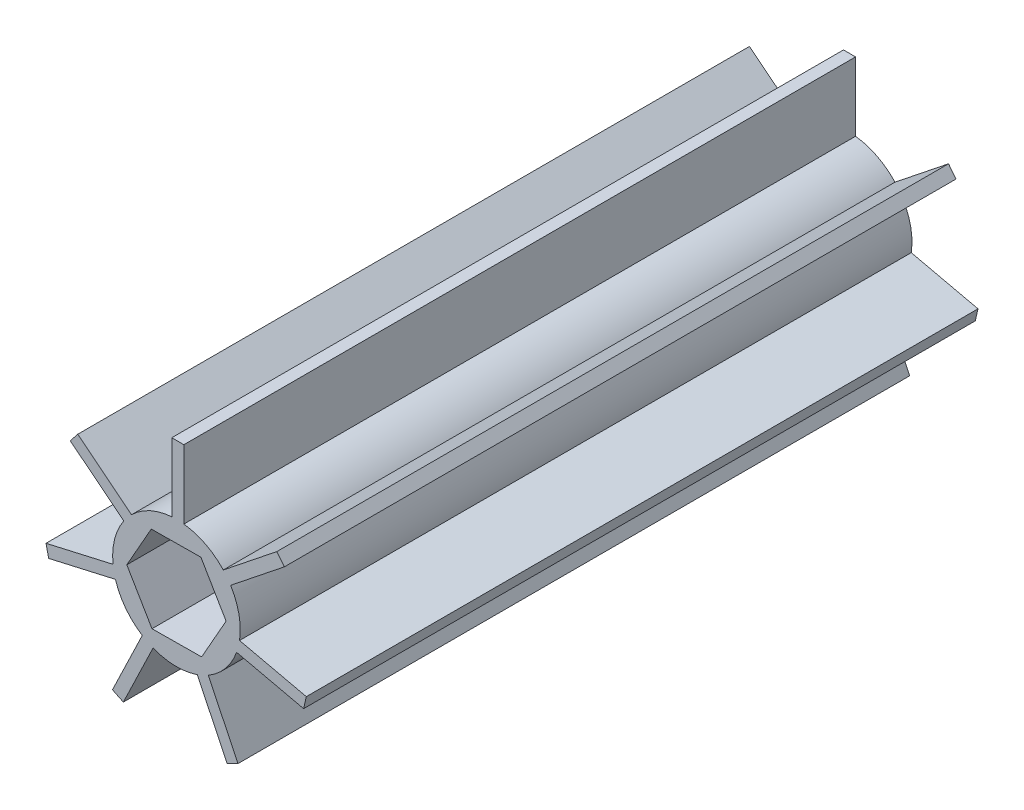
SolidWorks part; units mm, degrees
ref_plane "Front Plane" through (0, 0, 0) normal (0, 0, 1) x (1, 0, 0)
ref_plane "Top Plane" through (0, 0, 0) normal (0, 1, 0) x (1, 0, 0)
ref_plane "Right Plane" through (0, 0, 0) normal (1, 0, 0) x (0, 0, -1)
sketch "Sketch1" plane through (0, 0, 0) normal (0, 0, 1) x (1, 0, 0)
  circle A0 centre (0, 0) radius 15.0114
  dimension "D1" = 30.0228
sketch "Sketch6" plane through (0, 0, 0) normal (0, 0, 1) x (1, 0, 0)
  circle A0 centre (0, 0) radius 7.239
  dimension "D1" = 14.478
sketch "Sketch8" plane through (0, 0, 0) normal (0, 0, 1) x (1, 0, 0)
  line L1 (5.631, 0.0479) -> (2.7741, 4.9006)
  line L2 (2.7741, 4.9006) -> (-2.857, 4.8527)
  line L3 (-2.857, 4.8527) -> (-5.631, -0.0479)
  line L4 (-5.631, -0.0479) -> (-2.7741, -4.9006)
  line L5 (-2.7741, -4.9006) -> (2.857, -4.8527)
  line L6 (2.857, -4.8527) -> (5.631, 0.0479)
  circle A0 centre (0, 0) radius 4.8768 construction
  dimension "D1" = 4.8768
sketch "Sketch12" plane through (0, 0, 0) normal (0, 0, 1) x (1, 0, 0)
  line L0 (0, 0) -> (0.8406, 0)
  line L2 (-0.531, 0) -> (-0.531, 14.9878)
  line L3 (-0.531, 14.9878) -> (0.8406, 14.9878)
  line L4 (0.8406, 0) -> (0.8406, 14.9878)
  line L5 (0, 0) -> (0.8406, 14.9878) construction
  line L6 (-0.531, 14.9878) -> (0, 0) construction
  line L7 (0, 0) -> (-0.531, 0)
  circle A0 centre (0, 0) radius 15.0114 construction
  point P0 (0, 0)
  dimension "D1" = 1.3716
extrude "Boss-Extrude1" add sketch "Sketch12" against normal blind 76.2
extrude "Boss-Extrude2" add sketch "Sketch6" against normal blind 76.2 contours A0
ref_axis "Axis1" through (0, 0, -76.2) along (0, 0, 1)
pattern_circular "CirPattern1" count 7 over 360 about axis through (0, 0, -76.2) along (0, 0, 1) of "Boss-Extrude1"
extrude "Cut-Extrude5" cut sketch "Sketch8" against normal through all
